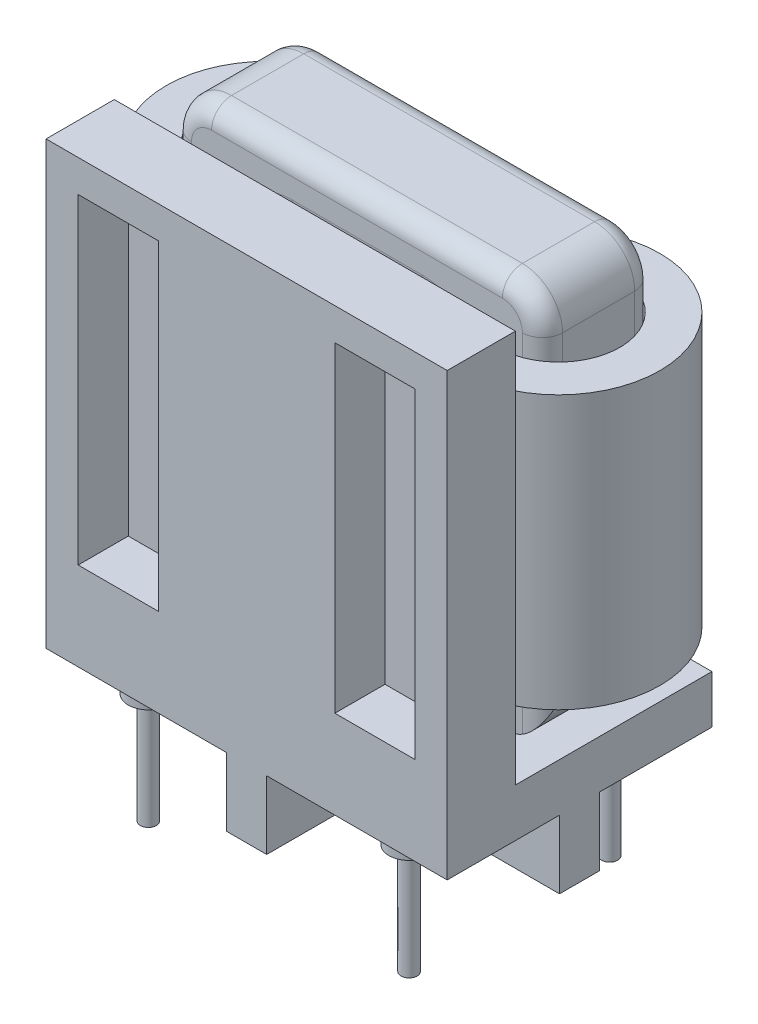
SolidWorks part; units mm, degrees
ref_plane "Front Plane" through (0, 0, 0) normal (0, 0, 1) x (1, 0, 0)
ref_plane "Top Plane" through (0, 0, 0) normal (0, 1, 0) x (1, 0, 0)
ref_plane "Right Plane" through (0, 0, 0) normal (1, 0, 0) x (0, 0, -1)
sketch "Sketch1" plane through (0, 0, 0) normal (0, 1, 0) x (1, 0, 0)
  line L1 (10, -1) -> (-10, -1)
  line L2 (10, -1) -> (10, 1)
  line L3 (10, 1) -> (-10, 1)
  line L4 (-10, -1) -> (-10, 1)
  line L5 (10, -1) -> (-10, 1) construction
  line L6 (10, 1) -> (-10, -1) construction
  line L7 (1, -6.6) -> (-1, -6.6)
  line L8 (1, -6.6) -> (1, 6.6)
  line L9 (1, 6.6) -> (-1, 6.6)
  line L10 (-1, -6.6) -> (-1, 6.6)
  line L11 (1, -6.6) -> (-1, 6.6) construction
  line L12 (1, 6.6) -> (-1, -6.6) construction
  point P0 (0, 0)
  point P6 (0, 0)
  dimension "D1" = 13.2
  dimension "D2" = 2
  dimension "D3" = 20
extrude "Boss-Extrude1" add sketch "Sketch1" along normal blind 3.4 contours L1 L10 L3 L4 | L10 L1 L8 L3 | L10 L3 L8 L9 | L10 L7 L8 L1 | L8 L1 L2 L3 region at (5.5, 0, 0) region at (0, 0, 3.8) region at (0, 0, 0) region at (-5.5, 0, 0) region at (0, 0, -3.8)
sketch "Sketch2" plane through (0, 3.4, 0) normal (0, 1, 0) x (1, 0, 0)
  line L0 (-10, 1) -> (-10, -49999) construction
  line L1 (-1, 6.6) -> (49999, 6.6) construction
  line L2 (-1, -6.6) -> (49999, -6.6) construction
  line L3 (10, -1) -> (10, 49999) construction
  line L5 (-10, 6.6) -> (10, 6.6)
  line L6 (-10, 6.6) -> (-10, -6.6)
  line L7 (-10, -6.6) -> (10, -6.6)
  line L8 (10, 6.6) -> (10, -6.6)
extrude "Boss-Extrude2" add sketch "Sketch2" along normal blind 2.4
sketch "Sketch3" plane through (0, 3.4, 0) normal (0, -1, 0) x (1, 0, 0)
  line L1 (6.5, 5) -> (-6.5, 5) construction
  line L2 (6.5, 5) -> (6.5, -5) construction
  line L3 (6.5, -5) -> (-6.5, -5) construction
  line L4 (-6.5, 5) -> (-6.5, -5) construction
  circle A0 centre (6.5, 5) radius 0.4
  circle A1 centre (-6.5, 5) radius 0.4
  circle A2 centre (-6.5, -5) radius 0.4
  circle A3 centre (6.5, -5) radius 0.4
  point P8 (0, -5)
  point P10 (6.5, 0)
  dimension "D3" = 0.8
  dimension "D1" = 13
  dimension "D2" = 10
extrude "Boss-Extrude3" add sketch "Sketch3" along normal blind 6.5
sketch "Sketch4" plane through (0, 3.4, 0) normal (0, -1, 0) x (1, 0, 0)
  circle A0 centre (6.5, 5) radius 1
  circle A1 centre (-6.5, 5) radius 1
  circle A2 centre (-6.5, -5) radius 1
  circle A3 centre (6.5, -5) radius 1
  dimension "D1" = 2
extrude "Boss-Extrude4" add sketch "Sketch4" along normal blind 1
sketch "Sketch5" plane through (0, 0, 6.6) normal (0, 0, 1) x (1, 0, 0)
  line L0 (10, 5.8) -> (10, 3.4) construction
  line L1 (-10, 5.8) -> (10, 5.8)
  line L2 (-10, 5.8) -> (-10, 25.4)
  line L3 (-10, 25.4) -> (10, 25.4)
  line L4 (10, 5.8) -> (10, 25.4)
  line L5 (1, 3.4) -> (10, 3.4) construction
  line L7 (-8.4, 23.8) -> (-4.4, 23.8)
  line L8 (-8.4, 23.8) -> (-8.4, 7.8)
  line L9 (-8.4, 7.8) -> (-4.4, 7.8)
  line L10 (-4.4, 23.8) -> (-4.4, 7.8)
  line L11 (8.4, 23.8) -> (4.4, 23.8)
  line L12 (8.4, 23.8) -> (8.4, 7.8)
  line L13 (8.4, 7.8) -> (4.4, 7.8)
  line L14 (4.4, 23.8) -> (4.4, 7.8)
  dimension "D1" = 22
  dimension "D2" = 16
  dimension "D3" = 4
  dimension "D4" = 1.6
  dimension "D5" = 1.6
  dimension "D6" = 1.6
extrude "Boss-Extrude5" add sketch "Sketch5" against normal blind 3.4
extrude "Boss-Extrude6" add sketch "Sketch5<2>" against normal up to surface (3.4 mm away) from offset 2.5 contours L10 L7 L8 L9 | L11 L14 L13 L12 region at (-6.4, 15.8, 6.6) region at (6.4, 15.8, 6.6) up to face at (6.4, 15.8, 3.2) offset against normal yes
sketch "Sketch5<2>" plane through (0, 0, 6.6) normal (0, 0, 1) x (1, 0, 0) same geometry as "Sketch5"
ref_plane "Plane1" through (0, 0, -1.7) normal (0, 0, -1) x (-1, 0, 0)
sketch "Sketch6" plane through (0, 0, -1.7) normal (0, 0, -1) x (-1, 0, 0)
  line L0 (10, 5.8) -> (-10, 5.8) construction
  line L1 (-7.25, 25.4) -> (7.25, 25.4)
  line L2 (-9.25, 23.4) -> (-9.25, 7.8)
  line L3 (-7.25, 5.8) -> (7.25, 5.8)
  line L4 (9.25, 23.4) -> (9.25, 7.8)
  line L5 (-10, 25.4) -> (10, 25.4) construction
  line L7 (-3.25, 22.4) -> (3.25, 22.4)
  line L8 (-5.25, 20.4) -> (-5.25, 10.8)
  line L9 (-3.25, 8.8) -> (3.25, 8.8)
  line L10 (5.25, 20.4) -> (5.25, 10.8)
  arc A0 (7.25, 25.4) -> (9.25, 23.4) centre (7.25, 23.4) cw
  arc A1 (7.25, 5.8) -> (9.25, 7.8) centre (7.25, 7.8) ccw
  arc A2 (-9.25, 7.8) -> (-7.25, 5.8) centre (-7.25, 7.8) ccw
  arc A3 (-7.25, 25.4) -> (-9.25, 23.4) centre (-7.25, 23.4) ccw
  arc A4 (-5.25, 10.8) -> (-3.25, 8.8) centre (-3.25, 10.8) ccw
  arc A5 (3.25, 8.8) -> (5.25, 10.8) centre (3.25, 10.8) ccw
  arc A6 (3.25, 22.4) -> (5.25, 20.4) centre (3.25, 20.4) cw
  arc A7 (-3.25, 22.4) -> (-5.25, 20.4) centre (-3.25, 20.4) ccw
  point P4 (0, 25.4)
  point P12 (9.25, 25.4)
  point P19 (-9.25, 25.4)
  dimension "D2" = 2
  dimension "D7" = 2
  dimension "D1" = 18.5
  dimension "D3" = 3
  dimension "D4" = 4
  dimension "D5" = 4
  dimension "D6" = 3
extrude "Boss-Extrude7" add sketch "Sketch6" along normal blind 2.8 and the other way blind 2.8
fillet "Fillet1" radius 1 8 edges at (4.6642, 9.3858, -4.5) (0, 8.8, -4.5) (-4.6642, 9.3858, -4.5) (-5.25, 15.6, -4.5) (-4.6642, 21.8142, -4.5) (0, 22.4, -4.5) (4.6642, 21.8142, -4.5) (5.25, 15.6, -4.5)
fillet "Fillet2" radius 1 8 edges at (0, 8.8, 1.1) (4.6642, 9.3858, 1.1) (5.25, 15.6, 1.1) (4.6642, 21.8142, 1.1) (0, 22.4, 1.1) (-4.6642, 21.8142, 1.1) (-5.25, 15.6, 1.1) (-4.6642, 9.3858, 1.1)
fillet "Fillet3" radius 1 10 edges at (-9.25, 15.6, 1.1) (-8.6642, 24.8142, 1.1) (9.25, 15.6, 1.1) (8.6642, 24.8142, 1.1) (0, 25.4, 1.1) (-9.25, 15.6, -4.5) (-8.6642, 24.8142, -4.5) (0, 25.4, -4.5) (9.25, 15.6, -4.5) (8.6642, 24.8142, -4.5) tangent propagation no
sketch "Sketch7" plane through (0, 8.8, 0) normal (0, 1, 0) x (1, 0, 0)
  line L0 (-9.25, -0.1) -> (-9.25, 3.5) construction
  line L1 (-9.25, -0.1) -> (-9.25, 3.5) construction
  line L2 (-5.25, -0.1) -> (-5.25, 3.5) construction
  line L3 (-5.25, -0.1) -> (-5.25, 3.5) construction
  line L4 (-9.25, 3.5) -> (-5.25, -0.1) construction
  line L5 (5.25, -0.1) -> (5.25, 3.5) construction
  line L6 (9.25, -0.1) -> (9.25, 3.5) construction
  line L7 (5.25, -0.1) -> (5.25, 3.5) construction
  line L8 (9.25, -0.1) -> (9.25, 3.5) construction
  line L9 (5.25, 3.5) -> (9.25, -0.1) construction
  circle A0 centre (-7.25, 1.7) radius 3.0591
  arc A1 (-5.25, 3.5) -> (-6.25, 4.5) centre (-6.25, 3.5) ccw construction
  arc A2 (-5.25, 3.5) -> (-6.25, 4.5) centre (-6.25, 3.5) ccw construction
  circle A3 centre (7.25, 1.7) radius 3.0591
  circle A4 centre (-7.25, 1.7) radius 5.0591
  circle A5 centre (7.25, 1.7) radius 5.0591
  dimension "D1" = 2
extrude "Boss-Extrude10" add sketch "Sketch7" along normal up to surface (13.6 mm away) separate body up to face at (0, 22.4, -1.7)
